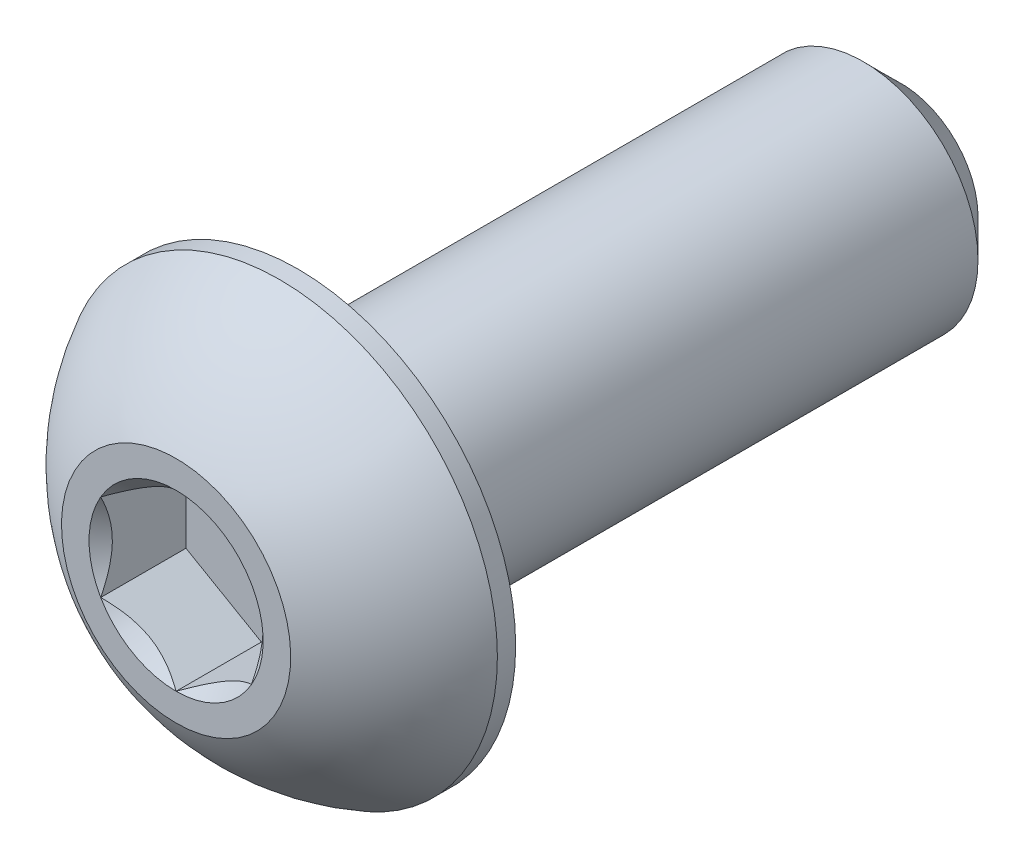
SolidWorks part; units mm, degrees
ref_plane "Front" through (0, 0, 0) normal (0, 0, 1) x (1, 0, 0)
ref_plane "Top" through (0, 0, 0) normal (0, 1, 0) x (1, 0, 0)
ref_plane "Right" through (0, 0, 0) normal (1, 0, 0) x (0, 0, -1)
sketch "Sketch1" plane through (0, 0, 0) normal (1, 0, 0) x (0, 0, -1)
  line L2 (2.5654, 2.413) -> (15.2654, 2.413)
  line L3 (15.2654, 2.413) -> (15.2654, 0)
  line L4 (15.2654, 0) -> (2.5654, 0)
  line L6 (2.1806, 4.5847) -> (2.5654, 4.5847) construction
  line L7 (15.2654, 2.413) -> (15.2654, -2.413) construction
  line L8 (0, 0) -> (2.5654, 0) construction
  line L9 (2.5654, 4.5847) -> (2.5654, -4.5847) construction
  line L11 (2.5654, 2.413) -> (2.5654, 0)
  line L13 (0, 1.5875) -> (0, -1.5875) construction
  line L14 (0, 1.5875) -> (0, 2.413) construction
  arc A3 (0, 2.413) -> (2.1806, 4.5847) centre (4.5749, 0) cw construction
  dimension "D1" = 0.3848
revolve "Revolve1" add sketch "Sketch1" angle 360 mid plane about L4
sketch "Sketch3" plane through (0, 0, -15.2654) normal (0, 0, -1) x (-1, 0, 0)
  circle A0 centre (0, 0) radius 2.413
curve "Helix/Spiral1" pitch 1.0583 height 13.7583 turns 13
sketch "Sketch2" plane through (0, 0, 0) normal (1, 0, 0) x (0, 0, -1)
  line L0 (15.2654, 2.413) -> (16.1914, 2.413)
  line L1 (16.1914, 2.413) -> (15.7946, 1.7256)
  line L2 (15.7946, 1.7256) -> (15.6623, 1.7256)
  line L3 (15.6623, 1.7256) -> (15.2654, 2.413)
  line L4 (15.4638, 2.0693) -> (15.993, 2.0693) construction
  dimension "D1" = 60
  dimension "D2" = 0.1323
  dimension "D3" = 0.5292
chamfer "Chamfer1" distance 0.7937 angle 45 1 edges at (0, 2.413, -15.2654)
sweep "Cut-Sweep1" [suppressed] cut profiles "Sketch2" path "Helix/Spiral1"
sketch "Sketch7" plane through (0, 0, 0) normal (1, 0, 0) x (0, 0, -1)
  line L6 (2.1806, 4.5847) -> (2.5654, 4.5847) construction
  line L8 (0, 0) -> (2.5654, 0) construction
  line L11 (2.5654, 4.5847) -> (2.5654, -4.5847) construction
  line L12 (2.1806, 4.5847) -> (2.5654, 4.5847)
  line L13 (0, 0) -> (2.5654, 0)
  line L14 (0, 1.5875) -> (0, -1.5875) construction
  line L15 (2.5654, 4.5847) -> (2.5654, 0)
  line L16 (0, 2.413) -> (0, 0)
  arc A2 (2.1806, 4.5847) -> (0, 2.413) centre (4.5749, 0) ccw construction
  arc A3 (2.1806, 4.5847) -> (0, 2.413) centre (4.5749, 0) ccw
revolve "Revolve2" add sketch "Sketch7" angle 360 mid plane about L13
sketch "Sketch5" plane through (0, 0, 0) normal (0, 0, 1) x (1, 0, 0)
  line L1 (1.5875, -0.9165) -> (1.5875, 0.9165)
  line L2 (1.5875, 0.9165) -> (0, 1.8331)
  line L3 (0, 1.8331) -> (-1.5875, 0.9165)
  line L4 (-1.5875, 0.9165) -> (-1.5875, -0.9165)
  line L5 (-1.5875, -0.9165) -> (0, -1.8331)
  line L6 (0, -1.8331) -> (1.5875, -0.9165)
  circle A0 centre (0, 0) radius 1.5875 construction
extrude "Cut-Extrude2" cut sketch "Sketch5" against normal blind 1.7958
sketch "Sketch6" plane through (0, 0, 0) normal (0, 0, 1) x (1, 0, 0)
  circle A0 centre (0, 0) radius 1.8331
extrude "Cut-Extrude3" cut sketch "Sketch6" against normal blind 1.7958 draft 45
sketch "Sketch9" [suppressed] plane through (0, 0, -2.2098) normal (0, 0, 1) x (1, 0, 0)
  circle A2 centre (0, 0) radius 2.0828
extrude "Boss-Extrude2" [suppressed] add sketch "Sketch9" against normal offset from surface (3.175 mm away) 22.225
sketch "Sketch10" plane through (0, 0, 0) normal (1, 0, 0) x (0, 0, -1)
  line L0 (15.2654, 2.413) -> (15.2654, -2.413) construction
  point P0 (13.6779, -2.413)
  dimension "D1" = 1.5875
equation "\"D3@Helix/Spiral1\" = \"Lg@Sketch1\" + \"D4@Helix/Spiral1\""
equation "\"D2@Sketch2\" = \"D4@Helix/Spiral1\" * .125"
equation "\"D3@Sketch2\" = \"D4@Helix/Spiral1\" * .5"
equation "\"D1@Chamfer1\" = \"D4@Helix/Spiral1\" * .75"
equation "\"D1@Cut-Extrude2\" = \"Head Ht@Sketch1\" * .7"
equation "\"D1@Sketch1\" = \"Head Ht@Sketch1\" * .15"
equation "\"D1@Sketch10\" = \"D4@Helix/Spiral1\" * 1.5"
equation "\"D1@Cut-Extrude3\" = \"D1@Cut-Extrude2\""
